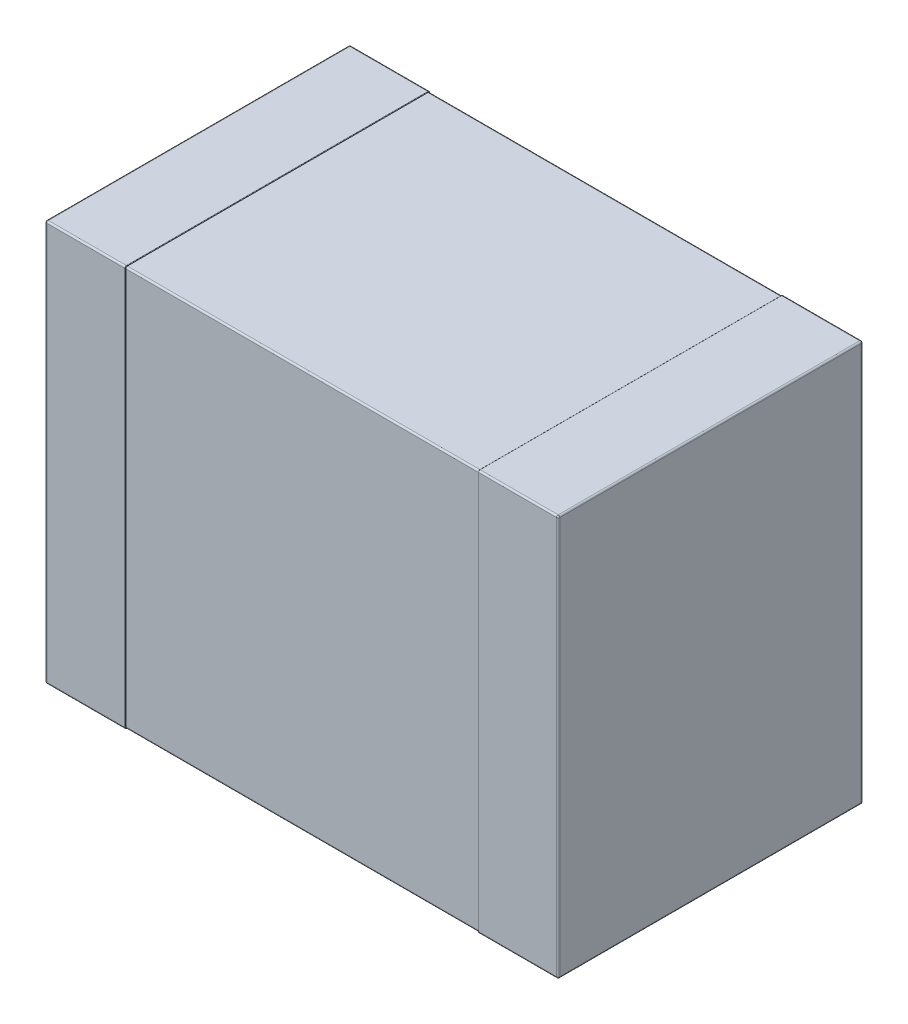
SolidWorks part; units mm, degrees
ref_plane "Top Plane" through (0, 0, 0) normal (0, 0, 1) x (1, 0, 0)
ref_plane "Front Plane" through (0, 0, 0) normal (0, 1, 0) x (1, 0, 0)
ref_plane "Side Plane" through (0, 0, 0) normal (1, 0, 0) x (0, 0, -1)
sketch "Sketch1" plane through (0, 0, 0) normal (0, 0, 1) x (1, 0, 0)
  line L1 (-1.6, 1.25) -> (1.6, 1.25)
  line L2 (-1.6, 1.25) -> (-1.6, -1.25)
  line L3 (-1.6, -1.25) -> (1.6, -1.25)
  line L4 (1.6, 1.25) -> (1.6, -1.25)
  dimension "D1" = 3.2
  dimension "D2" = 1.6
  dimension "D3" = 2.5
  dimension "D4" = 1.25
extrude "All body" add sketch "Sketch1" along normal blind 1.9
sketch "Sketch2" plane through (0, 0, 0) normal (1, 0, 0) x (0, 0, -1)
  line L14 (-0.003, 1.247) -> (-1.897, 1.247)
  line L15 (-0.003, -1.247) -> (-0.003, 1.247)
  line L16 (-1.897, -1.247) -> (-0.003, -1.247)
  line L17 (-1.897, 1.247) -> (-1.897, -1.247)
  line L18 (-0.003, 1.247) -> (-1.897, 1.247)
  line L19 (-0.003, -1.247) -> (-0.003, 1.247)
  line L20 (-1.897, -1.247) -> (-0.003, -1.247)
  line L21 (-1.897, 1.247) -> (-1.897, -1.247)
  dimension "D1" = 0.003
extrude "Cut out the body for pin" cut sketch "Sketch2" against normal blind 1.1 and the other way blind 1.1 flip side to cut
fillet "Body fillet" radius 0.01 4 edges at (0, 1.247, 0.003) (0, 1.247, 1.897) (0, -1.247, 0.003) (0, -1.247, 1.897)
fillet "Pin fillet a" radius 0.01 16 edges at (1.6, -1.25, 0.95) (1.6, 0, 1.9) (1.6, 1.25, 0.95) (1.6, 0, 0) (-1.6, 1.25, 0.95) (-1.6, 0, 1.9) (-1.6, -1.25, 0.95) (-1.6, 0, 0) (1.35, 1.25, 1.9) (1.35, -1.25, 1.9) (1.35, -1.25, 0) (1.35, 1.25, 0) (-1.35, 1.25, 0) (-1.35, -1.25, 0) (-1.35, 1.25, 1.9) (-1.35, -1.25, 1.9)
fillet "Pin fillet b" radius 0.003 16 edges at (1.1, -1.2471, 1.8971) (1.1, -1.25, 0.95) (1.1, -1.2471, 0.0029) (1.1, 0, 0) (1.1, 1.2471, 0.0029) (1.1, 1.25, 0.95) (1.1, 1.2471, 1.8971) (-1.1, -1.2471, 1.8971) (-1.1, -1.25, 0.95) (-1.1, -1.2471, 0.0029) (-1.1, 0, 0) (-1.1, 1.2471, 0.0029) (-1.1, 1.25, 0.95) (-1.1, 1.2471, 1.8971) (1.1, 0, 1.9) (-1.1, 0, 1.9)
